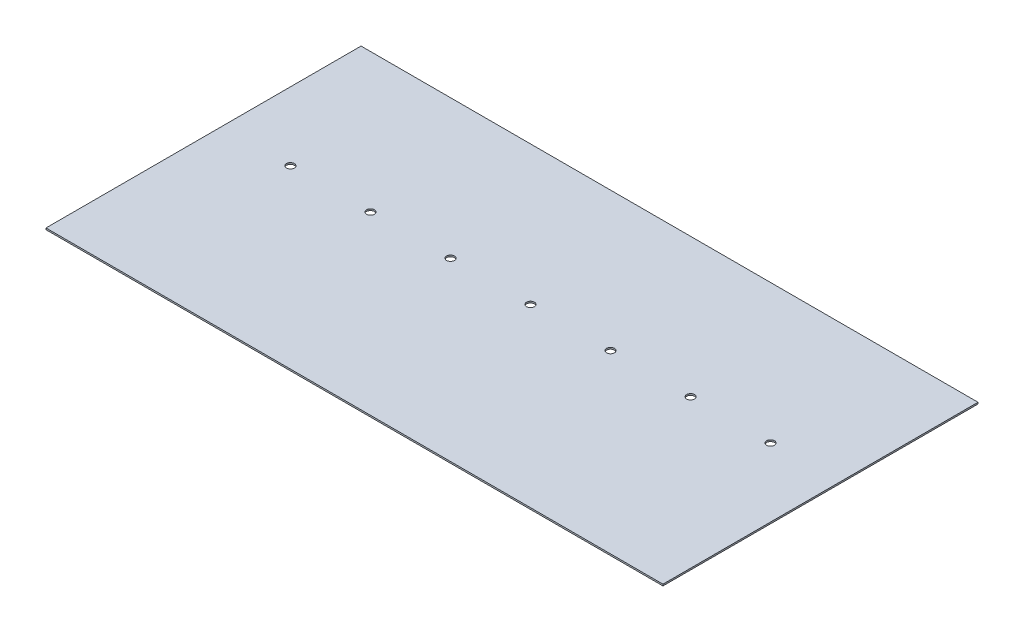
SolidWorks part; units mm, degrees
ref_plane "Front Plane" through (0, 0, 0) normal (0, 0, 1) x (1, 0, 0)
ref_plane "Top Plane" through (0, 0, 0) normal (0, 1, 0) x (1, 0, 0)
ref_plane "Right Plane" through (0, 0, 0) normal (1, 0, 0) x (0, 0, -1)
sketch "Sketch1" plane through (0, 0, 0) normal (0, 1, 0) x (1, 0, 0)
  line L0 (195.834, -199.9996) -> (195.834, -88.2396) construction
  line L1 (0, 0) -> (391.668, 0)
  line L2 (0, 0) -> (0, -199.9996)
  line L3 (0, -199.9996) -> (391.668, -199.9996)
  line L4 (391.668, 0) -> (391.668, -199.9996)
  line L5 (195.834, -88.2396) -> (391.668, -88.2396) construction
  line L6 (195.834, -88.2396) -> (0, -88.2396) construction
  circle A0 centre (195.834, -88.2396) radius 2.5
  circle A1 centre (145.034, -88.2396) radius 2.5
  circle A2 centre (94.234, -88.2396) radius 2.5
  circle A3 centre (43.434, -88.2396) radius 2.5
  circle A4 centre (195.834, -88.2396) radius 2.5
  circle A5 centre (145.034, -88.2396) radius 2.5
  circle A6 centre (94.234, -88.2396) radius 2.5
  circle A7 centre (246.634, -88.2396) radius 2.5
  circle A8 centre (195.834, -88.2396) radius 2.5
  circle A9 centre (145.034, -88.2396) radius 2.5
  circle A10 centre (297.434, -88.2396) radius 2.5
  circle A11 centre (246.634, -88.2396) radius 2.5
  circle A12 centre (195.834, -88.2396) radius 2.5
  circle A13 centre (246.634, -88.2396) radius 2.5
  circle A14 centre (297.434, -88.2396) radius 2.5
  circle A15 centre (348.234, -88.2396) radius 2.5
  dimension "D4" = 5
  dimension "D1" = 199.9996
  dimension "D2" = 391.668
  dimension "D3" = 111.76
  dimension "D5" = 4
  dimension "D6" = 4
extrude "Boss-Extrude1" add sketch "Sketch1" against normal blind 1 contours L4 L1 L2 L3 A15 A10 A7 A3 A2 A1 A0 region at (195.834, 0, 100.0205)
